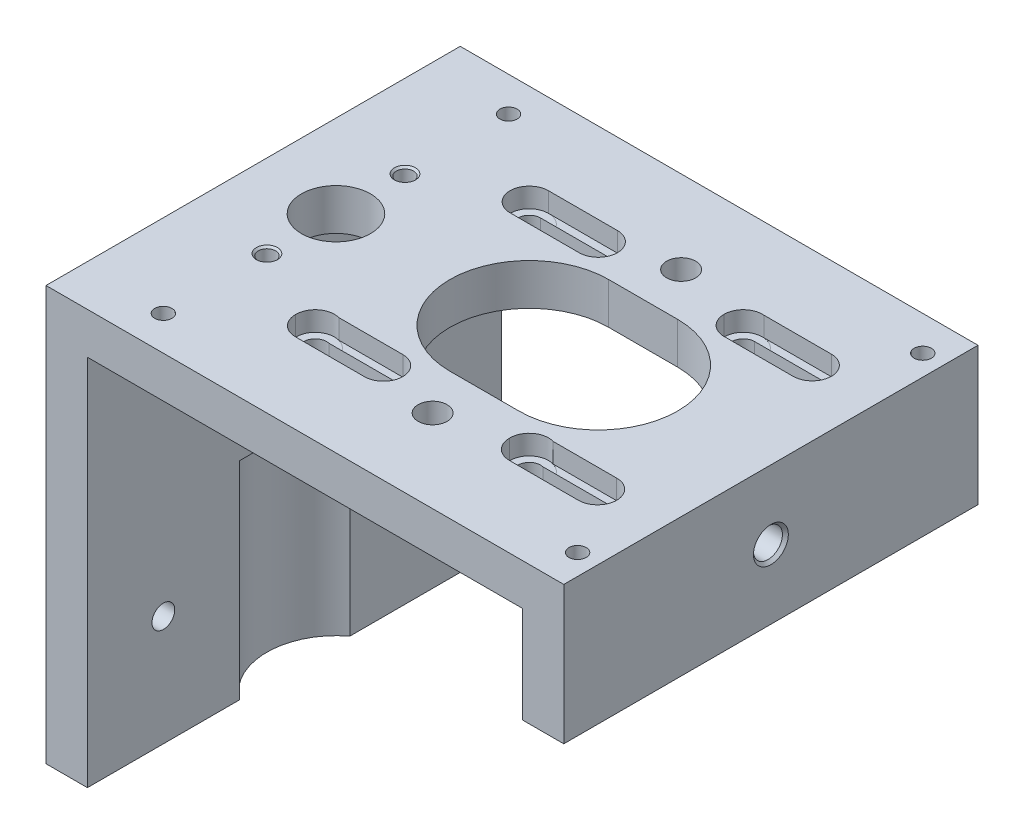
SolidWorks part; units mm, degrees
material "6061 Alloy"
ref_plane "Front Plane" through (0, 0, 0) normal (0, 0, 1) x (1, 0, 0)
ref_plane "Top Plane" through (0, 0, 0) normal (0, 1, 0) x (1, 0, 0)
ref_plane "Right Plane" through (0, 0, 0) normal (1, 0, 0) x (0, 0, -1)
sketch "Sketch1" plane through (0, 0, 0) normal (0, 0, 1) x (1, 0, 0)
  line L0 (0, 0) -> (6, 0)
  line L1 (69, 54) -> (69, 40)
  line L2 (0, 0) -> (0, 60)
  line L3 (0, 60) -> (75, 60)
  line L4 (75, 40) -> (75, 60)
  line L5 (69, 40) -> (75, 40)
  line L6 (6, 0) -> (6, 54)
  line L7 (6, 54) -> (69, 54)
  dimension "D1" = 75
  dimension "D2" = 6
  dimension "D3" = 6
  dimension "D4" = 60
  dimension "D5" = 20
  dimension "D6" = 6
extrude "Boss-Extrude1" add sketch "Sketch1" along normal blind 60
sketch "Sketch2" plane through (0, 60, 0) normal (0, 1, 0) x (1, 0, 0)
  line L0 (24.5, -45.5) -> (55.5, -45.5) construction
  line L1 (24.5, -45.5) -> (24.5, -14.5) construction
  line L2 (40, -18.5) -> (50, -18.5)
  line L3 (0, -60) -> (0, 0) construction
  line L4 (75, -30) -> (0, -30) construction
  line L5 (75, -60) -> (75, 0) construction
  line L6 (50, -41.5) -> (40, -41.5)
  arc A0 (40, -18.5) -> (40, -41.5) centre (40, -30) ccw
  arc A1 (50, -41.5) -> (50, -18.5) centre (50, -30) ccw
  circle A2 centre (40, -30) radius 11.5 construction
  point P2 (24.5, -45.5)
  point P3 (40, -45.5)
  point P4 (24.5, -30)
  point P5 (55.5, -45.5)
  point P6 (24.5, -14.5)
  point P7 (55.5, -14.5)
  dimension "D8" = 23
  dimension "D2" = 31
  dimension "D3" = 31
  dimension "D6" = 10
  dimension "D7" = 40
  dimension "D4" = 2
  dimension "D5" = 2
extrude "Cut-Extrude1" cut sketch "Sketch2" against normal through all
ref_axis "Axis1" through (40, 54, 30) along (0, 1, 0)
hole_wizard "CBORE for #4 Socket Head Cap Screw1" positions "Sketch7" profile "Sketch6" counterbore size "#4" standard "Ansi Inch" end condition through all
sketch "Sketch7" plane through (0, 60, 0) normal (0, 1, 0) x (-1, 0, 0)
  line L0 (-24.5, 45.5) -> (-55.5, 45.5) construction
  line L1 (-24.5, 45.5) -> (-24.5, 14.5) construction
  point P0 (-24.5, 45.5)
  point P8 (-55.5, 45.5)
  point P9 (-24.5, 14.5)
  point P10 (-55.5, 14.5)
  point P34 (-40, 45.5)
  point P35 (-24.5, 30)
  dimension "D1" = 31
  dimension "D4" = 31
  dimension "D2" = 2
  dimension "D3" = 2
sketch "Sketch6" plane through (24.5, 60, 45.5) normal (1, 0, 0) x (0, 0, 1)
  line L0 (0, 0) -> (0, 60)
  line L1 (0, 60) -> (1.6319, 60)
  line L3 (1.6319, 60) -> (1.632, 2.8448)
  line L4 (1.632, 2.8448) -> (2.7788, 2.8448)
  line L5 (2.7788, 2.8448) -> (2.7788, 0)
  line L7 (2.7788, 0) -> (0, 0)
  line L11 (0, -6.35) -> (0, 107.95) construction
  dimension "Thru Hole Dia." = 3.2639
  dimension "Thru Hole Depth" = 60
  dimension "C'Bore Dia." = 5.5575
  dimension "C'Bore Depth" = 2.8448
sketch "Sketch24" plane through (0, 60, 0) normal (0, 1, 0) x (1, 0, 0)
  line L0 (24.5, -14.5) -> (34.5, -14.5) construction
  line L1 (24.5, -12.868) -> (34.5, -12.868)
  line L2 (24.5, -16.132) -> (34.5, -16.132)
  line L3 (65.5138, -30) -> (17.4578, -30) construction
  line L4 (55.5, -14.5) -> (65.5, -14.5) construction
  line L5 (55.5, -12.868) -> (65.5, -12.868)
  line L6 (55.5, -16.132) -> (65.5, -16.132)
  line L7 (24.5, -45.543) -> (34.5, -45.543) construction
  line L8 (24.5, -43.911) -> (34.5, -43.911)
  line L9 (24.5, -47.1749) -> (34.5, -47.1749)
  line L10 (55.5, -45.543) -> (65.5, -45.543) construction
  line L11 (55.5, -43.911) -> (65.5, -43.911)
  line L12 (55.5, -47.1749) -> (65.5, -47.1749)
  line L13 (40, -9.8721) -> (40, -50.1279) construction
  arc A0 (24.5, -12.868) -> (24.5, -16.132) centre (24.5, -14.5) ccw
  arc A1 (34.5, -16.132) -> (34.5, -12.868) centre (34.5, -14.5) ccw
  circle A2 centre (24.5, -14.5) radius 1.632 construction
  arc A3 (55.5, -12.868) -> (55.5, -16.132) centre (55.5, -14.5) ccw
  arc A4 (65.5, -16.132) -> (65.5, -12.868) centre (65.5, -14.5) ccw
  arc A5 (24.5, -43.911) -> (24.5, -47.1749) centre (24.5, -45.543) ccw
  arc A6 (34.5, -47.1749) -> (34.5, -43.911) centre (34.5, -45.543) ccw
  arc A7 (55.5, -43.911) -> (55.5, -47.1749) centre (55.5, -45.543) ccw
  arc A8 (65.5, -47.1749) -> (65.5, -43.911) centre (65.5, -45.543) ccw
  point P3 (29.5, -14.5)
  point P18 (60.5, -14.5)
  point P25 (29.5, -45.543)
  point P32 (60.5, -45.543)
  dimension "D1" = 10
  dimension "D2" = 2
  dimension "D3" = 2
extrude "Cut-Extrude5" cut sketch "Sketch24" against normal up to next
sketch "Sketch25" plane through (0, 60, 0) normal (0, 1, 0) x (1, 0, 0)
  line L0 (24.5, -14.5) -> (34.5, -14.5) construction
  line L1 (24.5, -11.7212) -> (34.5, -11.7212)
  line L2 (24.5, -17.2788) -> (34.5, -17.2788)
  line L3 (55.5, -14.5099) -> (65.5, -14.5099) construction
  line L4 (55.5, -11.7311) -> (65.5, -11.7311)
  line L5 (55.5, -17.2886) -> (65.5, -17.2886)
  line L6 (24.5, -45.6008) -> (34.5, -45.6008) construction
  line L7 (24.5, -42.8221) -> (34.5, -42.8221)
  line L8 (24.5, -48.3796) -> (34.5, -48.3796)
  line L9 (55.5, -45.6107) -> (65.5, -45.6107) construction
  line L10 (55.5, -42.832) -> (65.5, -42.832)
  line L11 (55.5, -48.3895) -> (65.5, -48.3895)
  arc A0 (24.5, -11.7212) -> (24.5, -17.2788) centre (24.5, -14.5) ccw
  arc A1 (34.5, -17.2788) -> (34.5, -11.7212) centre (34.5, -14.5) ccw
  arc A2 (26.7491, -12.868) -> (26.7491, -16.132) centre (24.5, -14.5) ccw construction
  arc A3 (55.5, -11.7311) -> (55.5, -17.2886) centre (55.5, -14.5099) ccw
  arc A4 (65.5, -17.2886) -> (65.5, -11.7311) centre (65.5, -14.5099) ccw
  arc A5 (24.5, -42.8221) -> (24.5, -48.3796) centre (24.5, -45.6008) ccw
  arc A6 (34.5, -48.3796) -> (34.5, -42.8221) centre (34.5, -45.6008) ccw
  arc A7 (55.5, -42.832) -> (55.5, -48.3895) centre (55.5, -45.6107) ccw
  arc A8 (65.5, -48.3895) -> (65.5, -42.832) centre (65.5, -45.6107) ccw
  point P4 (29.5, -14.5)
  point P17 (60.5, -14.5099)
  point P24 (29.5, -45.6008)
  point P31 (60.5, -45.6107)
  dimension "D1" = 10
  dimension "D2" = 2
  dimension "D3" = 2
extrude "Cut-Extrude6" cut sketch "Sketch25" against normal blind 2.84
hole_wizard "M3 Tapped Hole1" positions "Sketch9" profile "Sketch10" tap size "M3" standard "ISO"
sketch "Sketch9" plane through (0, 60, 0) normal (0, 1, 0) x (-1, 0, 0)
  line L0 (-12, 55) -> (-72, 55) construction
  line L1 (-12, 55) -> (-12, 5) construction
  line L20 (-75, 60) -> (0, 60) construction
  line L21 (0, 60) -> (0, 0) construction
  point P1 (-12, 55)
  point P5 (-72, 55)
  point P6 (-12, 5)
  point P7 (-72, 5)
  dimension "D1" = 60
  dimension "D2" = 50
  dimension "D6" = 5
  dimension "D7" = 12
  dimension "D3" = 2
  dimension "D4" = 2
sketch "Sketch10" plane through (12, 60, 55) normal (1, 0, 0) x (0, 0, 1)
  line L0 (0, 0) -> (0, 9.2511)
  line L1 (0, 9.2511) -> (1.25, 8.5)
  line L2 (1.25, 8.5) -> (1.25, 0)
  line L5 (1.25, 0) -> (0, 0)
  line L10 (0, 9.2511) -> (-1.25, 8.5) construction
  line L11 (0, -6.35) -> (0, 107.95) construction
  dimension "Tap Drill Dia." = 2.5
  dimension "Tap Drill Depth" = 8.5
  dimension "Drill Angle" = 118
cosmetic thread "Hole Thread1" parameters "D1"=6, "D2"=3
cosmetic thread "Hole Thread2" parameters "D1"=6, "D2"=3
cosmetic thread "Hole Thread3" parameters "D1"=6, "D2"=3
cosmetic thread "Hole Thread4" parameters "D1"=6, "D2"=3
hole_wizard "M5 Tapped Hole1" positions "Sketch14" profile "Sketch15" tap size "M5" standard "ISO" end condition through all
sketch "Sketch14" plane through (0, 60, 0) normal (0, 1, 0) x (-1, 0, 0)
  line L0 (-44, 12) -> (-44, 48) construction
  point P0 (-44, 12)
  point P1 (-44, 48)
  dimension "D1" = 18
  dimension "D2" = 18
  dimension "D3" = 4
sketch "Sketch15" plane through (44, 60, 12) normal (1, 0, 0) x (0, 0, 1)
  line L0 (0, 0) -> (0, 60)
  line L1 (0, 60) -> (2.1, 60)
  line L2 (2.1, 60) -> (2.1, 0)
  line L5 (2.1, 0) -> (0, 0)
  line L11 (0, -6.35) -> (0, 107.95) construction
  dimension "Thru Tap Drill Dia." = 4.2
  dimension "Thru Tap Drill Depth" = 60
cosmetic thread "Hole Thread5" parameters "D2"=5
cosmetic thread "Hole Thread6" parameters "D2"=5
sketch "Sketch11" plane through (0, 60, 0) normal (0, 1, 0) x (1, 0, 0)
  line L1 (0, -60) -> (0, 0) construction
  line L2 (75, -30) -> (0, -30) construction
  line L3 (75, -60) -> (75, 0) construction
  circle A0 centre (12, -30) radius 5
  dimension "D2" = 10
  dimension "D1" = 12
extrude "Cut-Extrude2" cut sketch "Sketch11" against normal through all
ref_axis "Axis2" through (12, 54, 30) along (0, 1, 0)
hole_wizard "M4 Tapped Hole1" positions "Sketch20" profile "Sketch19" tap size "M4" standard "ISO" end condition up to next
sketch "Sketch20" plane through (0, 0, 0) normal (-1, 0, 0) x (0, 0, 1)
  line L0 (30, 60) -> (30, 0) construction
  line L1 (60, 60) -> (0, 60) construction
  line L2 (60, 0) -> (0, 0) construction
  point P0 (11, 46)
  point P13 (11, 16)
  point P16 (49, 46)
  point P18 (49, 16)
  dimension "D1" = 14
  dimension "D2" = 30
  dimension "D3" = 38
cosmetic thread "Hole Thread7" parameters "D2"=4
cosmetic thread "Hole Thread8" parameters "D2"=4
cosmetic thread "Hole Thread9" parameters "D2"=4
cosmetic thread "Hole Thread10" parameters "D2"=4
sketch "Sketch19" plane through (0, 46, 11) normal (0, 1, 0) x (0, 0, 1)
  line L0 (0, 0) -> (0, 6)
  line L1 (0, 6) -> (1.65, 6)
  line L2 (1.65, 6) -> (1.65, 0.6)
  line L3 (1.65, 0.6) -> (2.25, 0)
  line L5 (2.25, 0) -> (0, 0)
  line L6 (-1.65, 0.6) -> (-2.25, 0) construction
  line L11 (0, -6.35) -> (0, 107.95) construction
  dimension "Thru Tap Drill Dia." = 3.3
  dimension "Thru Tap Drill Depth" = 6
  dimension "Near C'Sink Dia." = 4.5
  dimension "Near C'Sink Angle" = 90
hole_wizard "M5 Tapped Hole2" positions "Sketch23" profile "Sketch22" tap size "M5" standard "ISO" end condition up to next
sketch "Sketch23" plane through (75, 0, 0) normal (1, 0, 0) x (0, 0, -1)
  line L0 (-30, 54) -> (-30, 60) construction
  line L1 (-60, 60) -> (0, 60) construction
  point P0 (-30, 50)
  dimension "D1" = 10
cosmetic thread "Hole Thread11" parameters "D2"=5
sketch "Sketch22" plane through (75, 50, 30) normal (0, 1, 0) x (0, 0, -1)
  line L0 (0, 0) -> (0, 6)
  line L1 (0, 6) -> (2.1, 6)
  line L2 (2.1, 6) -> (2.1, 0.425)
  line L3 (2.1, 0.425) -> (2.525, 0)
  line L5 (2.525, 0) -> (0, 0)
  line L6 (-2.1, 0.425) -> (-2.525, 0) construction
  line L11 (0, -6.35) -> (0, 107.95) construction
  dimension "Thru Tap Drill Dia." = 4.2
  dimension "Thru Tap Drill Depth" = 6
  dimension "Near C'Sink Dia." = 5.05
  dimension "Near C'Sink Angle" = 90
sketch "Sketch16" plane through (0, 0, 0) normal (0, -1, 0) x (1, 0, 0)
  circle A0 centre (12, 30) radius 10
extrude "Cut-Extrude4" cut sketch "Sketch16" against normal blind 30
hole_wizard "M3 Tapped Hole2" positions "Sketch28" profile "Sketch29" tap size "M3" standard "ISO" end condition up to next
sketch "Sketch28" plane through (0, 54, 0) normal (0, -1, 0) x (1, 0, 0)
  line L0 (12, 43.3514) -> (12, 16.6486) construction
  line L2 (20.0951, 30) -> (3.9049, 30) construction
  point P12 (12, 40)
  point P26 (12, 20)
  dimension "D1" = 20
cosmetic thread "Hole Thread12" parameters "D2"=3
cosmetic thread "Hole Thread13" parameters "D2"=3
sketch "Sketch29" plane through (12, 54, 40) normal (1, 0, 0) x (0, 0, -1)
  line L0 (0, 0) -> (0, 6)
  line L1 (0, 6) -> (1.525, 6)
  line L2 (1.25, 5.725) -> (1.25, 0.275)
  line L3 (1.25, 0.275) -> (1.525, 0)
  line L5 (1.525, 0) -> (0, 0)
  line L6 (-1.25, 0.275) -> (-1.525, 0) construction
  line L7 (1.525, 6) -> (1.25, 5.725)
  line L8 (-1.525, 6) -> (-1.25, 5.725) construction
  line L11 (0, -6.35) -> (0, 107.95) construction
  dimension "Thru Tap Drill Dia." = 2.5
  dimension "Thru Tap Drill Depth" = 6
  dimension "Near C'Sink Dia." = 3.05
  dimension "Near C'Sink Angle" = 90
  dimension "Far C'Sink Dia." = 3.05
  dimension "Far C'Sink Angle" = 90
